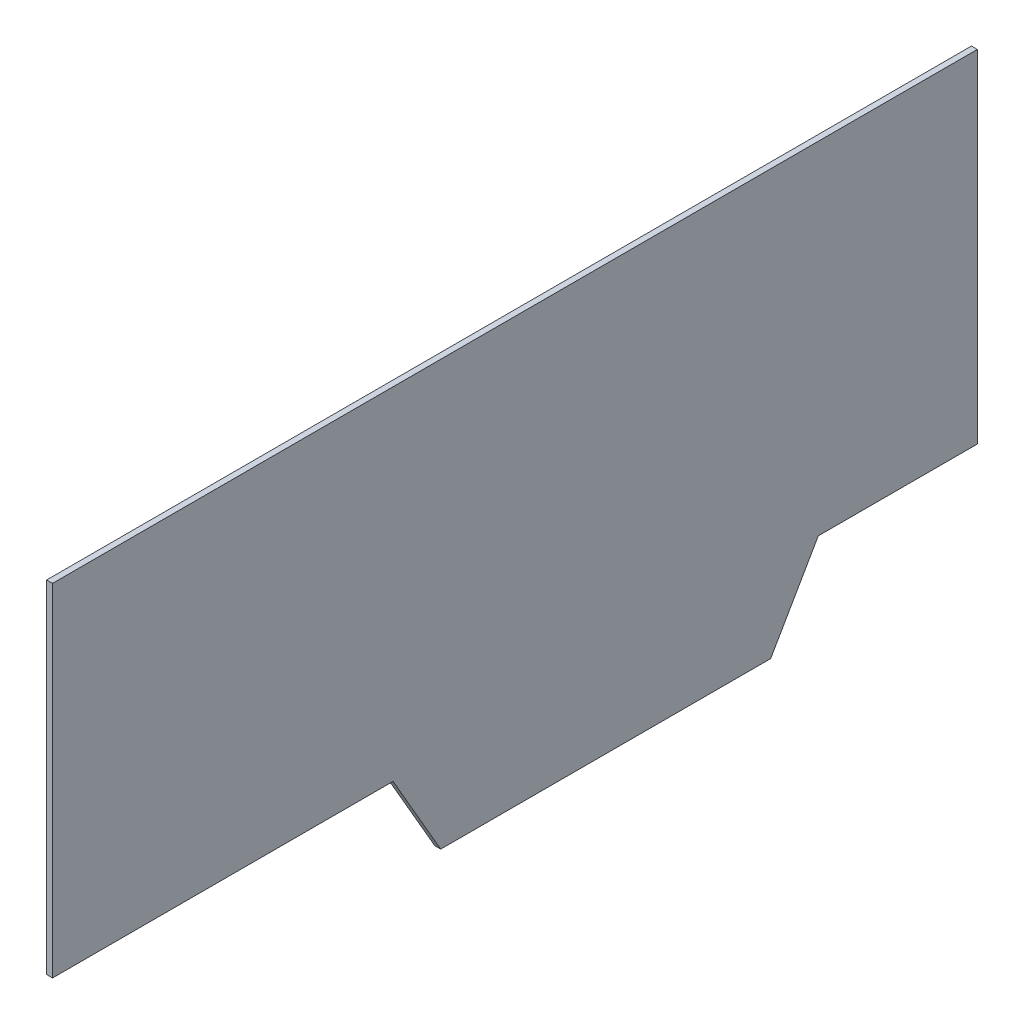
SolidWorks part; units mm, degrees
material "6061-T6 (SS)"
ref_plane "X-Y Datum" through (0, 0, 0) normal (0, 0, 1) x (1, 0, 0)
ref_plane "X-Z Datum" through (0, 0, 0) normal (0, 1, 0) x (1, 0, 0)
ref_plane "Y-Z Datum" through (0, 0, 0) normal (1, 0, 0) x (0, 0, -1)
sketch "Sketch1" plane through (0, 0, 0) normal (1, 0, 0) x (0, 0, -1)
  line L1 (-249.174, 88.9) -> (249.174, 88.9)
  line L2 (-249.174, 88.9) -> (-249.174, -88.9)
  line L3 (-249.174, -88.9) -> (249.174, -88.9)
  line L4 (249.174, 88.9) -> (249.174, -88.9)
  line L5 (-249.174, 88.9) -> (249.174, -88.9) construction
  line L6 (-249.174, -88.9) -> (249.174, 88.9) construction
  point P0 (0, 0)
  dimension "D1" = 177.8
  dimension "D2" = 498.348
extrude "Boss-Extrude1" add sketch "Sketch1" along normal mid plane 3.175
sketch "Sketch2" plane through (1.5875, 0, 0) normal (1, 0, 0) x (0, 0, -1)
  line L0 (249.174, -88.9) -> (249.174, -95.25)
  line L1 (249.174, -95.25) -> (163.449, -95.25)
  line L2 (163.449, -95.25) -> (137.7858, -139.7)
  line L3 (137.7858, -139.7) -> (-40.0142, -139.7)
  line L5 (-249.174, -88.9) -> (249.174, -88.9) construction
  line L6 (-249.174, -88.9) -> (249.174, -88.9)
  line L7 (-40.0142, -139.7) -> (-65.6774, -95.25)
  line L8 (-65.6774, -95.25) -> (-249.174, -95.25)
  line L9 (-249.174, -95.25) -> (-249.174, -88.9)
  line L10 (249.174, -88.9) -> (249.174, 88.9) construction
  line L11 (-249.174, 88.9) -> (-249.174, -88.9) construction
  point P15 (-245.999, -88.9)
  line M10 (-249.174, -88.9) -> (249.174, -88.9)
  dimension "D1" = 6.35
  dimension "D2" = 85.725
  dimension "D3" = 50.8
  dimension "D4" = 177.8
  dimension "D5" = 6.35
  dimension "D6" = 120
  dimension "D7" = 120
extrude "Boss-Extrude2" add sketch "Sketch2" against normal blind 3.175 contours L3 L2 L1 L0 M10 region at (1.5875, -110.1989, -36.2143)
